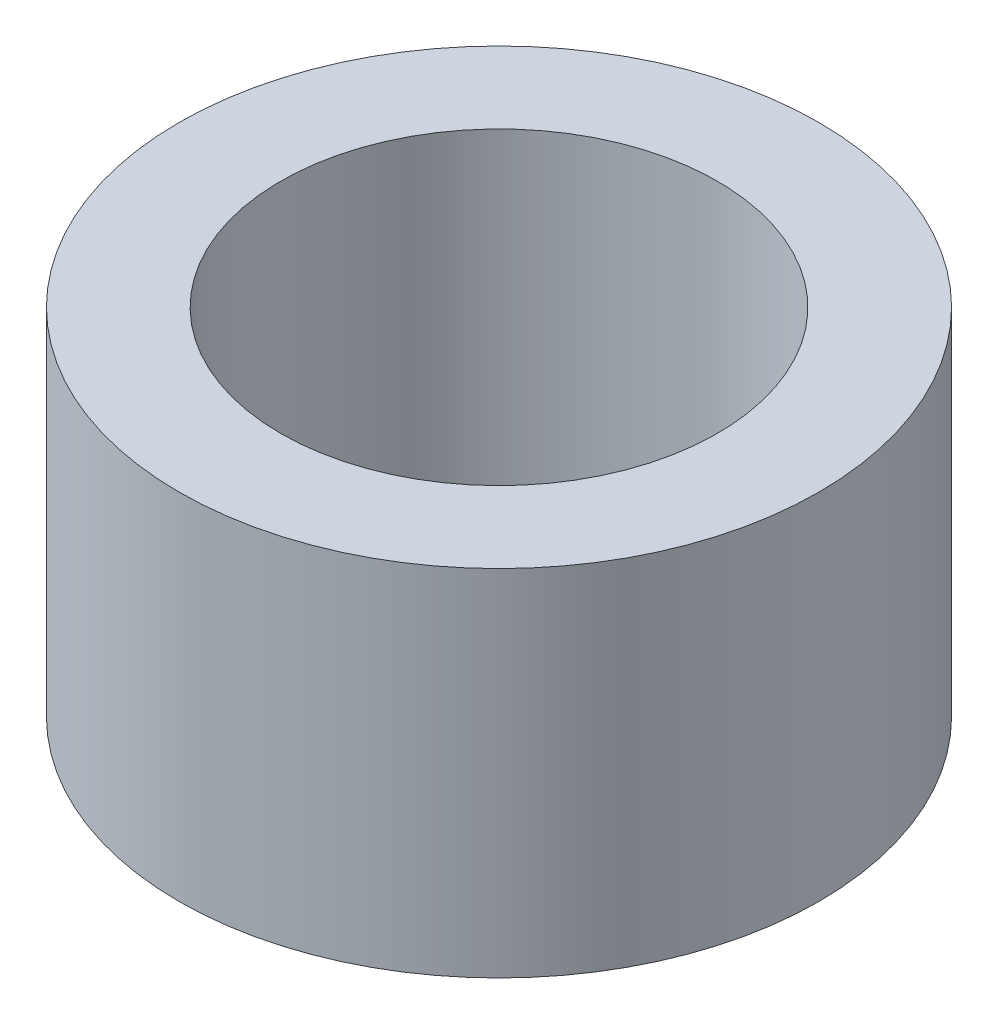
SolidWorks part; units mm, degrees
ref_plane "Front Plane" through (0, 0, 0) normal (0, 0, 1) x (1, 0, 0)
ref_plane "Top Plane" through (0, 0, 0) normal (0, 1, 0) x (1, 0, 0)
ref_plane "Right Plane" through (0, 0, 0) normal (1, 0, 0) x (0, 0, -1)
sketch "Sketch1" plane through (0, 0, 0) normal (0, 1, 0) x (1, 0, 0)
  circle A0 centre (0, 0) radius 8.001
  circle A1 centre (0, 0) radius 5.461
  dimension "D1" = 16.002
  dimension "D2" = 10.922
extrude "Boss-Extrude1" add sketch "Sketch1" along normal blind 8.8644 contours A1 | A0 A1 region at (-7.7747, 0, 0) region at (0, 0, 0)
sketch "Sketch2" plane through (0, 0, 0) normal (0, 0, 1) x (1, 0, 0)
  line L0 (0, 0) -> (0, -3.1356)
  line L1 (0, -3.1356) -> (8.001, 0)
  line L2 (8.001, 0) -> (0, 0)
  dimension "D1" = 21.4
revolve "Revolve1" add sketch "Sketch2" angle 360 about L0
extrude "Cut-Extrude1" cut sketch "Sketch1<6>" against normal blind 9.46 from surface contours A1 region at (0, 0, 0) starting at face at (0, 8.8644, 8.001)
sketch "Sketch1<6>" plane through (0, 0, 0) normal (0, 1, 0) x (1, 0, 0) same geometry as "Sketch1"
equation "\"OldSchoolLengthHoles\"= 2.5in'OldSchool > NewSchool"
equation "\"SchoolWidthHoles\"= 1.625in'OldSchool = NewSchool"
equation "\"Angle\"= 40deg'Looks about <= 40deg"
equation "\"Width\"= 2.125in'Pretty sure this is standardized on longboard and skateboard"
equation "\"Length\"= 3in'Will have some variation?"
equation "\"NewSchoolLengthHoles\"= 2.125in'NewSchool Mounting"
equation "\"HoleSize\"= ( 3in / 16 )'hole"
equation "\"Depth\"= 1in / 8'Assuming same depth as a riserplate"
equation "\"KingpinBoltSize\"= 3in / 8"
equation "\"PivotCupDia\"= 0.63in'0.7in (large) 0.626 (small)"
equation "\"PivotCupDepth\"= 12mm'15mm (large) 12mm (small)"
equation "\"PivotCupEndAngle\"= 21.4' Assuming it is indy pivots"
equation "\"PivotCupInnerDia\"= 0.43in'0.5in (large) 0.43 (small)"
equation "\"D1@Sketch1\"=\"PivotCupDia\""
equation "\"D2@Sketch1\"=\"PivotCupInnerDia\""
equation "\"D1@Boss-Extrude1\"=\"PivotCupDepth\"-\"PivotCupDia\"/2*tan(\"PivotCupEndAngle\")"
equation "\"D3\"= 90 - \"PivotCupEndAngle\""
equation "\"D1@Cut-Extrude1\"=\"PivotCupDepth\"-(\"PivotCupDia\"-\"PivotCupInnerDia\")/2"
